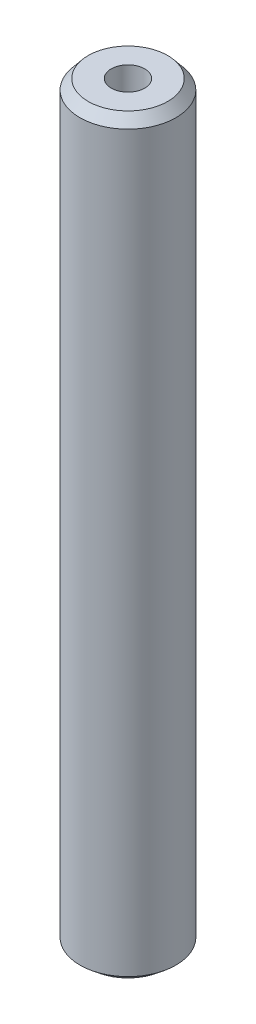
SolidWorks part; units mm, degrees
ref_plane "Front Plane" through (0, 0, 0) normal (0, 0, 1) x (1, 0, 0)
ref_plane "Top Plane" through (0, 0, 0) normal (0, 1, 0) x (1, 0, 0)
ref_plane "Right Plane" through (0, 0, 0) normal (1, 0, 0) x (0, 0, -1)
sketch "Sketch1" plane through (0, 0, 0) normal (0, 1, 0) x (1, 0, 0)
  circle A0 centre (0, 0) radius 27.5
  dimension "SHAFT_OD" = 55
extrude "Boss-Extrude1" add sketch "Sketch1" along normal blind 430.6856
sketch "Sketch2" plane through (0, 0, 0) normal (0, 1, 0) x (1, 0, 0)
  circle A0 centre (0, 0) radius 9.5984
  dimension "BORE_D" = 19.1969
extrude "Cut-Extrude1" cut sketch "Sketch2" along normal through all
chamfer "Chamfer1" distance 5.703 angle 39.58 2 edges at (0, 430.6856, 27.5) (0, 0, 27.5) first distance on face at (0, 430.6856, 27.5) first distance on face at (0, 0, 9.5984)
